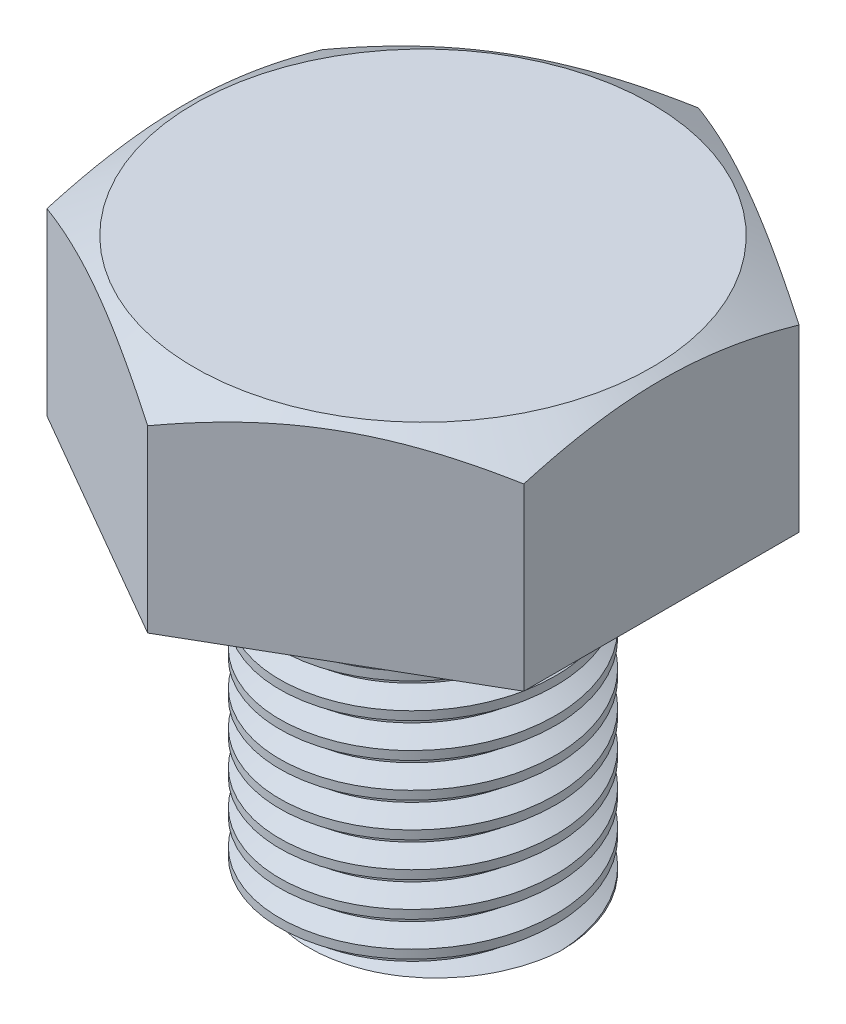
SolidWorks part; units mm, degrees
ref_plane "Front Plane" through (0, 0, 0) normal (0, 0, 1) x (1, 0, 0)
ref_plane "Top Plane" through (0, 0, 0) normal (0, 1, 0) x (1, 0, 0)
ref_plane "Right Plane" through (0, 0, 0) normal (1, 0, 0) x (0, 0, -1)
sketch "Sketch1" plane through (0, 0, 0) normal (0, 0, 1) x (1, 0, 0)
  line L0 (0, 0) -> (8, 0)
  line L1 (8, 0) -> (8, 20)
  line L2 (8, 20) -> (16, 20)
  line L3 (16, 20) -> (16, 32)
  line L4 (16, 32) -> (0, 32)
  line L5 (0, 32) -> (0, 0)
  dimension "D1" = 8
  dimension "D2" = 16
  dimension "D3" = 20
  dimension "D4" = 12
revolve "Revolve1" add sketch "Sketch1" angle 360 about L5
thread "Thread1" pitch 2 method cut trim with start face yes profile "Thread Profile1" start angle 0, offset 2, length 20, pitch 2, diameter 16
ref_plane "Plane1" through (8, -2, 0) normal (0, 0, -1) x (-1, 0, 0)
sketch "Thread Profile1" plane through (8, -2, 0) normal (0, 0, -1) x (-1, 0, 0)
  line L0 (0, 0) -> (0, 2) construction
  line L1 (0, 0) -> (1.0825, 0.625)
  line L2 (1.0825, 0.625) -> (1.0825, 0.875)
  line L3 (1.0825, 0.875) -> (0, 1.5)
  line L4 (1.0825, 0.75) -> (0, 0.75) construction
  line L11 (0, 0) -> (0, 1.5)
  point P2 (0, 0)
  dimension "Pitch" = 2
  dimension "Profile_Angle" = 60
  dimension "Profile_Land" = 0.25
  dimension "Profile_Height" = 1.0825
sketch "Sketch5" plane through (0, 32, 0) normal (0, 1, 0) x (1, 0, 0)
  line L1 (0, 16) -> (-13.8564, 8)
  line L2 (-13.8564, 8) -> (-13.8564, -8)
  line L3 (-13.8564, -8) -> (0, -16)
  line L4 (0, -16) -> (13.8564, -8)
  line L5 (13.8564, -8) -> (13.8564, 8)
  line L6 (13.8564, 8) -> (0, 16)
  circle A0 centre (0, 0) radius 13.8564 construction
  point P1 (0, 0)
  dimension "D1" = 32
extrude "Cut-Extrude1" cut sketch "Sketch5" against normal through all flip side to cut
sketch "Sketch7" plane through (0, 0, 0) normal (1, 0, 0) x (0, 0, -1)
  line L3 (0, 0) -> (0, 28.2734) construction
  line L4 (16, 32) -> (16, 30.4314)
  line L5 (16, 20) -> (16, 32) construction
  line L6 (16, 30.4314) -> (13.283, 32)
  line L7 (13.283, 32) -> (16, 32)
  point P8 (13.283, 32)
  dimension "D1" = 30
revolve "Cut-Revolve3" cut sketch "Sketch7" angle 360 about L3
